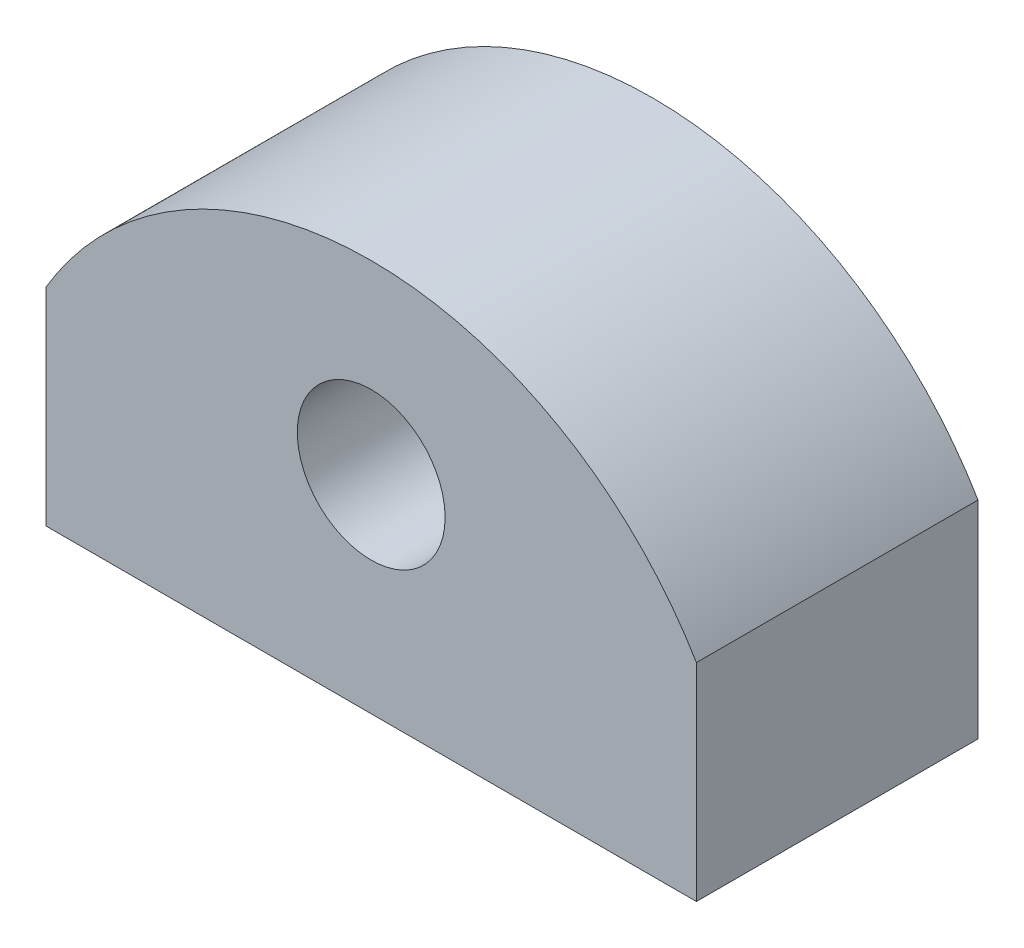
SolidWorks part; units mm, degrees
material "6061 Alloy"
ref_plane "Front Plane" through (0, 0, 0) normal (0, 0, 1) x (1, 0, 0)
ref_plane "Top Plane" through (0, 0, 0) normal (0, 1, 0) x (1, 0, 0)
ref_plane "Right Plane" through (0, 0, 0) normal (1, 0, 0) x (0, 0, -1)
sketch "Sketch1" plane through (0, 0, 0) normal (0, 0, 1) x (1, 0, 0)
  line L1 (-11, 3.5) -> (11, 3.5) construction
  line L2 (-11, 3.5) -> (-11, -3.5)
  line L3 (-11, -3.5) -> (11, -3.5)
  line L4 (11, 3.5) -> (11, -3.5)
  line L5 (0, -3.5) -> (0, -3) construction
  line L6 (-11, 0) -> (11, 0) construction
  arc A0 (-11, 3.5) -> (11, 3.5) centre (0, -3) cw
  point P0 (0, 0)
  point P5 (0, 0)
  dimension "D1" = 22
  dimension "D2" = 7
  dimension "D3" = 3
extrude "Boss-Extrude1" add sketch "Sketch1" along normal blind 9.525
sketch "Sketch2" plane through (0, 0, 9.525) normal (0, 0, 1) x (1, 0, 0)
  line L0 (-11, 3.5) -> (11, 3.5) construction
  circle A0 centre (0, 3.5) radius 2.5
  point P4 (0, 0)
  dimension "D1" = 5
extrude "M5_DRILL" cut sketch "Sketch2" against normal up to surface (9.525 mm away) up to face at (0, 1.5692, 0)
sketch "Sketch3" plane through (0, -3.5, 0) normal (0, -1, 0) x (1, 0, 0)
  line L0 (-11, 4.7625) -> (11, 4.7625) construction
  line L1 (-11, 9.525) -> (-11, 0) construction
  line L2 (11, 9.525) -> (11, 0) construction
  line L3 (0, 0) -> (0, 9.525) construction
  line L4 (-11, 9.525) -> (11, 9.525) construction
  circle A0 centre (-6, 4.7625) radius 2
  circle A1 centre (6, 4.7625) radius 2
  dimension "D1" = 4
  dimension "D2" = 6
extrude "M4_DRILL" cut sketch "Sketch3" against normal blind 8
